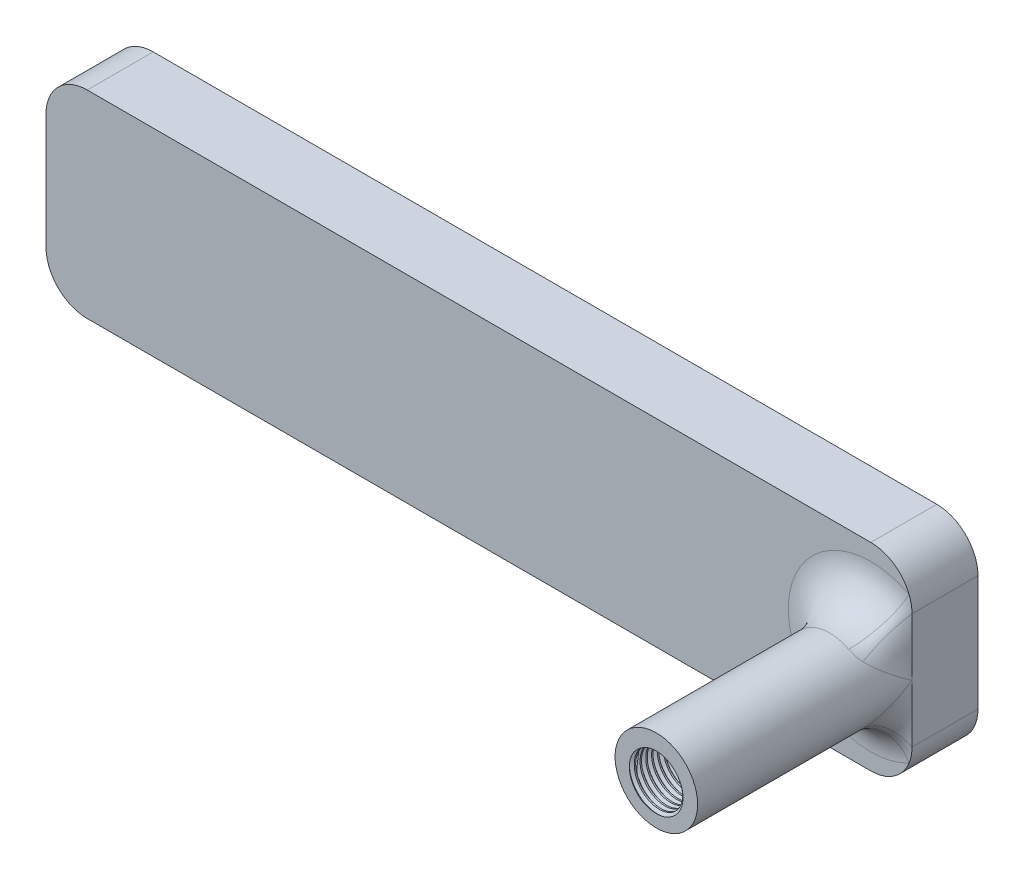
SolidWorks part; units mm, degrees
ref_plane "正面" through (0, 0, 0) normal (0, 0, 1) x (1, 0, 0)
ref_plane "平面" through (0, 0, 0) normal (0, 1, 0) x (1, 0, 0)
ref_plane "右側面" through (0, 0, 0) normal (1, 0, 0) x (0, 0, -1)
sketch "ｽｹｯﾁ1" plane through (0, 0, 0) normal (0, 0, 1) x (1, 0, 0)
  circle A1 centre (0, 0) radius 5
  dimension "D1" = 10
extrude "ﾎﾞｽ - 押し出し1" add sketch "ｽｹｯﾁ1" against normal blind 26 and the other way blind 5
sketch "ｽｹｯﾁ2" plane through (0, 0, -26) normal (0, 0, -1) x (-1, 0, 0)
  circle A0 centre (0, 0) radius 3.1
  dimension "D1" = 6.2
extrude "ｶｯﾄ - 押し出し1" cut sketch "ｽｹｯﾁ2" against normal through all
thread "ねじ山2" pitch 0.7 method cut profile "ねじ山の輪郭2" start angle 0, offset 0, length 20, pitch 0.7, diameter 6.2
ref_plane "平面2" through (-3.1, 0, 5) normal (0, -1, 0) x (-1, 0, 0)
sketch "ねじ山の輪郭2" plane through (-3.1, 0, 5) normal (0, -1, 0) x (-1, 0, 0)
  line L0 (0, 0) -> (0, 0.7) construction
  line L1 (0, 0) -> (0.3789, 0.2187)
  line L2 (0.3789, 0.2187) -> (0.3789, 0.3062)
  line L3 (0.3789, 0.3062) -> (0, 0.525)
  line L4 (0.3789, 0.2625) -> (0, 0.2625) construction
  line L11 (0, 0) -> (0, 0.525)
  point P2 (0, 0)
  dimension "Pitch" = 0.7
  dimension "Profile_Angle" = 60
  dimension "Profile_Land" = 0.0875
  dimension "Profile_Height" = 0.3789
sketch "ｽｹｯﾁ13" plane through (0, 0, 5) normal (0, 0, 1) x (1, 0, 0)
  circle A0 centre (0, 0) radius 8.4706
extrude "ｶｯﾄ - 押し出し6" cut sketch "ｽｹｯﾁ13" against normal blind 5
sketch "ｽｹｯﾁ19" plane through (0, 0, -26) normal (0, 0, -1) x (-1, 0, 0)
  line L0 (-5, 7) -> (-5, -7)
  line L1 (0, -12) -> (95, -12)
  line L2 (100, -7) -> (100, 7)
  line L3 (95, 12) -> (0, 12)
  arc A0 (-5, -7) -> (0, -12) centre (0, -7) ccw
  arc A1 (95, -12) -> (100, -7) centre (95, -7) ccw
  arc A2 (100, 7) -> (95, 12) centre (95, 7) ccw
  arc A3 (0, 12) -> (-5, 7) centre (0, 7) ccw
  circle A4 centre (0, 0) radius 5 construction
  point P16 (-5, 0)
  dimension "D1" = 95
  dimension "D2" = 24
extrude "ﾎﾞｽ - 押し出し5" add sketch "ｽｹｯﾁ19" along normal blind 8
fillet "ﾌｨﾚｯﾄ1" radius 5 1 edges at (5, 0, -26)
sketch "ｽｹｯﾁ20" plane through (0, 0, -34) normal (0, 0, -1) x (-1, 0, 0)
  line L1 (4.5, 7) -> (18.75, 7) construction
  line L2 (18.75, 7) -> (33, 7) construction
  line L3 (33, 7) -> (47.25, 7) construction
  line L4 (47.25, 7) -> (61.5, 7) construction
  line L5 (61.5, 7) -> (75.75, 7) construction
  line L6 (75.75, 7) -> (90, 7) construction
  line L7 (4.5, -7) -> (18.75, -7) construction
  line L8 (4.5, 0) -> (18.75, 0) construction
  line L9 (18.75, 0) -> (33, 0) construction
  line L10 (33, 0) -> (47.25, 0) construction
  line L11 (47.25, 0) -> (61.5, 0) construction
  line L12 (61.5, 0) -> (75.75, 0) construction
  line L13 (75.75, 0) -> (90, 0) construction
  line L14 (100, -7) -> (100, 7) construction
  line L16 (18.75, -7) -> (33, -7) construction
  line L17 (33, -7) -> (47.25, -7) construction
  line L18 (47.25, -7) -> (61.5, -7) construction
  line L19 (61.5, -7) -> (75.75, -7) construction
  line L20 (75.75, -7) -> (90, -7) construction
  line L21 (4.5, 7) -> (4.5, 0) construction
  line L22 (4.5, 0) -> (4.5, -7) construction
  line L23 (-5, 7) -> (-5, -7) construction
  circle A3 centre (33, 7) radius 3.2
  circle A4 centre (47.25, 7) radius 3.2
  circle A5 centre (61.5, 7) radius 3.2
  circle A6 centre (75.75, 7) radius 3.2
  circle A7 centre (90, 7) radius 3.2
  circle A11 centre (33, 0) radius 3.2
  circle A12 centre (47.25, 0) radius 3.2
  circle A13 centre (61.5, 0) radius 3.2
  circle A14 centre (75.75, 0) radius 3.2
  circle A15 centre (90, 0) radius 3.2
  circle A22 centre (33, -7) radius 3.2
  circle A23 centre (47.25, -7) radius 3.2
  circle A24 centre (61.5, -7) radius 3.2
  circle A25 centre (75.75, -7) radius 3.2
  circle A26 centre (90, -7) radius 3.2
  dimension "D1" = 38
  dimension "D3" = 6.4
  dimension "D2" = 10
extrude "ｶｯﾄ - 押し出し9" cut sketch "ｽｹｯﾁ20" against normal blind 3.2
